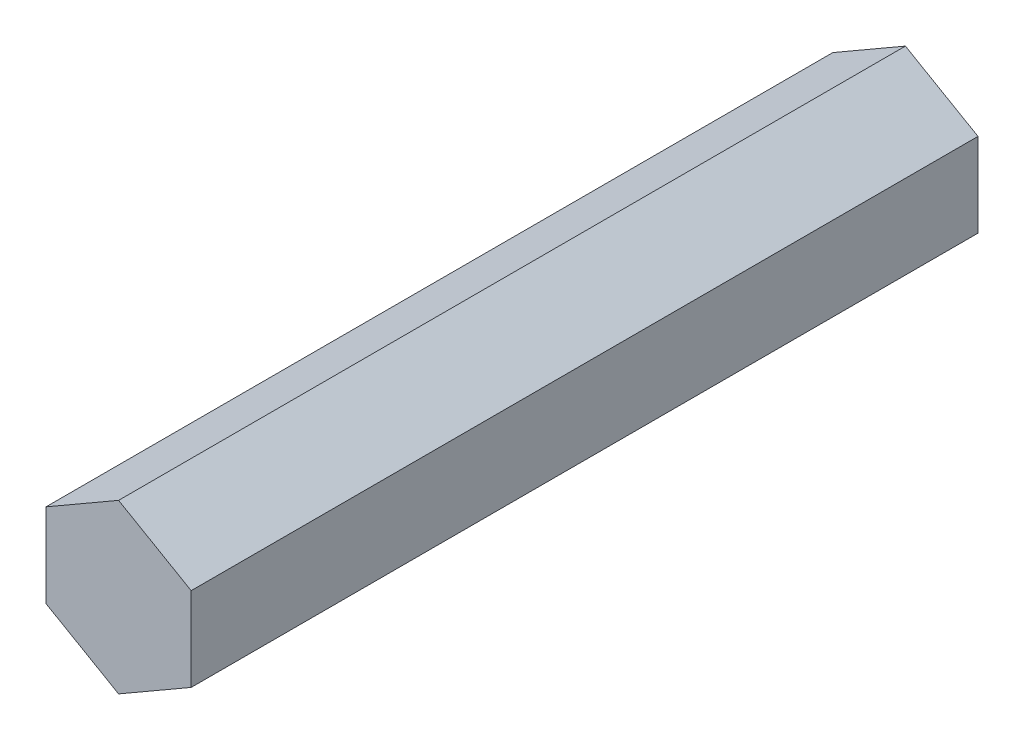
SolidWorks part; units mm, degrees
ref_plane "Front Plane" through (0, 0, 0) normal (0, 0, 1) x (1, 0, 0)
ref_plane "Top Plane" through (0, 0, 0) normal (0, 1, 0) x (1, 0, 0)
ref_plane "Right Plane" through (0, 0, 0) normal (1, 0, 0) x (0, 0, -1)
sketch "Sketch1" plane through (0, 0, 0) normal (0, 0, 1) x (1, 0, 0)
  line L1 (6.35, 3.6662) -> (0, 7.3323)
  line L2 (0, 7.3323) -> (-6.35, 3.6662)
  line L3 (-6.35, 3.6662) -> (-6.35, -3.6662)
  line L4 (-6.35, -3.6662) -> (0, -7.3323)
  line L5 (0, -7.3323) -> (6.35, -3.6662)
  line L6 (6.35, -3.6662) -> (6.35, 3.6662)
  circle A0 centre (0, 0) radius 6.35 construction
  dimension "D1" = 12.7
extrude "Boss-Extrude1" add sketch "Sketch1" along normal mid plane 68.834 contours L3 L4 L5 L6 L1 L2
ref_axis "Axis1" through (0, 0, -8.89) along (0, 0, 1)
